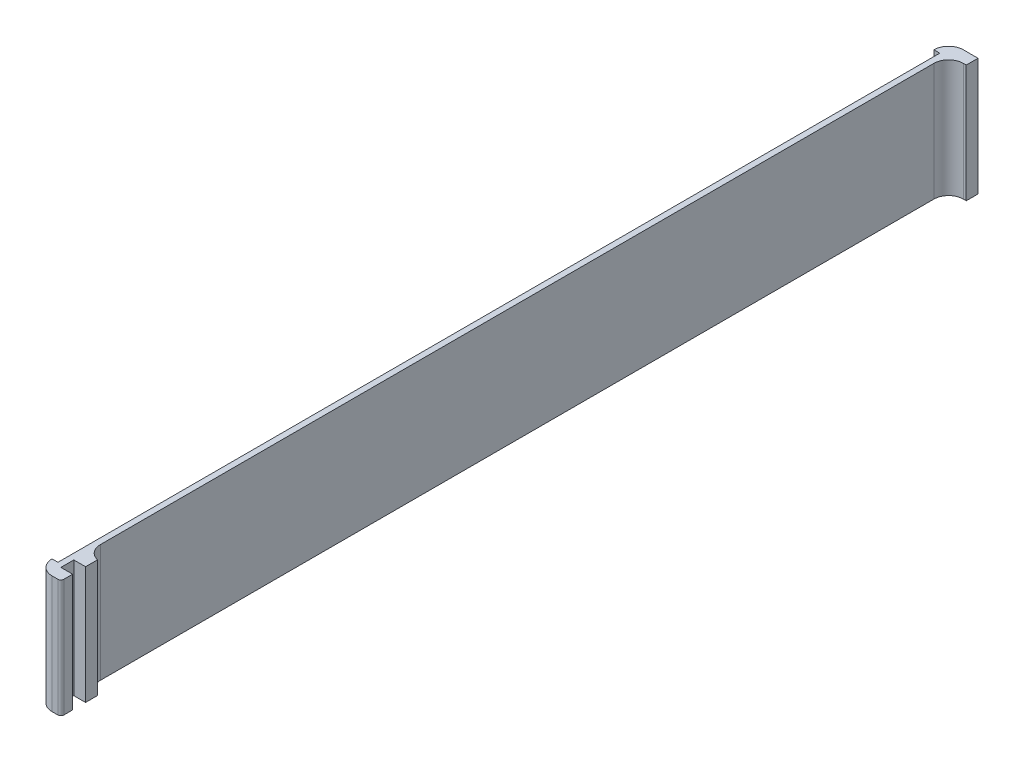
SolidWorks part; units mm, degrees
ref_plane "Front Plane" through (0, 0, 0) normal (0, 0, 1) x (1, 0, 0)
ref_plane "Top Plane" through (0, 0, 0) normal (0, 1, 0) x (1, 0, 0)
ref_plane "Right Plane" through (0, 0, 0) normal (1, 0, 0) x (0, 0, -1)
sketch "Sketch1" plane through (0, 0, 0) normal (0, 1, 0) x (1, 0, 0)
  line L1 (-19.5, 77.5) -> (19.5, 77.5)
  line L2 (-19.5, 77.5) -> (-19.5, -77.5)
  line L3 (-19.5, -77.5) -> (19.5, -77.5)
  line L4 (19.5, 77.5) -> (19.5, -77.5)
  line L5 (-19.5, 77.5) -> (19.5, -77.5) construction
  line L6 (-19.5, -77.5) -> (19.5, 77.5) construction
  point P0 (0, 0)
  dimension "D1" = 39
  dimension "D2" = 155
extrude "Boss-Extrude1" add sketch "Sketch1" along normal blind 2
sketch "Sketch2" plane through (0, 2, 0) normal (0, 1, 0) x (1, 0, 0)
  line L0 (-17.5, -75.5) -> (-17.5, -77.5)
  line L1 (-19.5, 77.5) -> (19.5, 77.5)
  line L2 (-19.5, 77.5) -> (-19.5, -77.5)
  line L3 (-19.5, -77.5) -> (19.5, -77.5)
  line L4 (19.5, 77.5) -> (19.5, -77.5)
  line L5 (-17.5, 75.5) -> (17.5, 75.5)
  line L6 (-17.5, 75.5) -> (-17.5, -75.5)
  line L7 (-17.5, -75.5) -> (17.5, -75.5)
  line L8 (17.5, 75.5) -> (17.5, -75.5)
  line L9 (-17.5, 75.5) -> (17.5, -75.5) construction
  line L10 (-17.5, -75.5) -> (17.5, 75.5) construction
  line L11 (17.5, -75.5) -> (17.5, -77.5)
  point P6 (0, 0)
  line M9 (19.5, -77.5) -> (19.5, 77.5)
  line M10 (19.5, 77.5) -> (-19.5, 77.5)
  line M11 (-19.5, 77.5) -> (-19.5, -77.5)
  line M12 (-19.5, -77.5) -> (19.5, -77.5)
  dimension "D1" = 2
  dimension "D2" = 2
extrude "Boss-Extrude2" add sketch "Sketch2" along normal blind 38 contours L8 L11 L3 L0 L6 L5 M9 M10 M11 M12 region at (-19.0983, 2, 76.5)
sketch "Sketch3" plane through (0, 2, 0) normal (0, 1, 0) x (1, 0, 0)
  line L0 (-17.5, 75.5) -> (-17.5, -77.5) construction
  line L1 (-17.5, -77.5) -> (-15.5, -77.5)
  line L2 (-17.5, -77.5) -> (-17.5, -75.5)
  line L3 (-17.5, -75.5) -> (-15.5, -75.5)
  line L4 (-15.5, -77.5) -> (-15.5, -75.5)
  line L5 (-17.5, -73.3) -> (-15.5, -73.3)
  line L6 (-17.5, -73.3) -> (-17.5, -71.3)
  line L7 (-17.5, -71.3) -> (-15.5, -71.3)
  line L8 (-15.5, -73.3) -> (-15.5, -71.3)
  line L9 (17.5, 75.5) -> (17.5, -77.5) construction
  line L10 (17.5, -77.5) -> (15.5, -77.5)
  line L11 (17.5, -77.5) -> (17.5, -75.5)
  line L12 (17.5, -75.5) -> (15.5, -75.5)
  line L13 (15.5, -77.5) -> (15.5, -75.5)
  line L14 (17.5, -73.3) -> (15.5, -73.3)
  line L15 (17.5, -73.3) -> (17.5, -71.3)
  line L16 (17.5, -71.3) -> (15.5, -71.3)
  line L17 (15.5, -73.3) -> (15.5, -71.3)
  line L18 (15.5, -75.5) -> (15.5, -73.3) construction
  line L19 (-15.5, -73.3) -> (15.5, -73.3) construction
  line L20 (-15.5, -75.5) -> (-15.5, -73.3) construction
  line L21 (-15.5, -75.5) -> (15.5, -75.5) construction
  line L22 (15.5, -71.3) -> (-15.5, -71.3) construction
  dimension "D1" = 2
  dimension "D2" = 2
  dimension "D3" = 2.2
  dimension "D4" = 2
extrude "Boss-Extrude3" add sketch "Sketch3" along normal up to surface (38 mm away) up to face at (0, 40, 0.5)
sketch "Sketch4" plane through (0, 0, -75.5) normal (0, 0, 1) x (1, 0, 0)
  line L0 (-17.5, 40) -> (-15.5, 40)
  line L1 (-17.5, 40) -> (17.5, 40) construction
  line L2 (-15.5, 40) -> (-15.5, 38)
  line L3 (-15.5, 38) -> (-17.5, 38)
  line L5 (-17.5, 38) -> (-17.5, 40)
  line L7 (-17.5, 40) -> (-17.5, 2) construction
  line L8 (-15.5, 33.8) -> (-17.5, 31.8)
  line L9 (-17.5, 31.8) -> (-17.5, 35.8)
  line L10 (-15.5, 33.8) -> (-15.5, 35.8)
  line L11 (-15.5, 35.8) -> (-17.5, 35.8)
  line L12 (0, 0) -> (0, 40) construction
  line L13 (15.5, 35.8) -> (17.5, 35.8)
  line L14 (15.5, 33.8) -> (15.5, 35.8)
  line L15 (17.5, 31.8) -> (17.5, 35.8)
  line L16 (15.5, 33.8) -> (17.5, 31.8)
  line L17 (17.5, 38) -> (17.5, 40)
  line L18 (15.5, 38) -> (17.5, 38)
  line L19 (15.5, 40) -> (15.5, 38)
  line L20 (17.5, 40) -> (15.5, 40)
  dimension "D1" = 2
  dimension "D2" = 2
  dimension "D3" = 45
  dimension "D4" = 2.2
  dimension "D5" = 2
extrude "Boss-Extrude4" add sketch "Sketch4" along normal up to surface (153 mm away) up to face at (0, 20.5, 77.5)
sketch "Sketch5" plane through (0, 2, 0) normal (0, 1, 0) x (1, 0, 0)
  line L1 (-15.5, -77.5) -> (15.5, -77.5)
  line L2 (-15.5, -77.5) -> (-15.5, -75.5)
  line L3 (-15.5, -75.5) -> (15.5, -75.5)
  line L4 (15.5, -77.5) -> (15.5, -75.5)
  line L5 (-15.5, -71.3) -> (15.5, -71.3)
  line L6 (-15.5, -71.3) -> (-15.5, -73.3)
  line L7 (-15.5, -73.3) -> (15.5, -73.3)
  line L8 (15.5, -71.3) -> (15.5, -73.3)
sketch "Sketch6" plane through (0, 0, -75.5) normal (0, 0, 1) x (1, 0, 0)
  line L0 (-17.5, 38) -> (-15.5, 38) construction
  line L1 (-17.5, 38) -> (17.5, 38)
  line L2 (-17.5, 38) -> (-17.5, 35.8)
  line L3 (-17.5, 35.8) -> (17.5, 35.8)
  line L4 (17.5, 38) -> (17.5, 35.8)
  line L5 (-17.5, 38) -> (-17.5, 35.8) construction
  line L6 (-15.5, 35.8) -> (-17.5, 35.8) construction
extrude "Cut-Extrude1" cut sketch "Sketch6" along normal through all
sketch "Sketch7" plane through (0, 2, 0) normal (0, 1, 0) x (1, 0, 0)
  line L1 (-17.5, -75.5) -> (17.5, -75.5)
  line L2 (-17.5, -75.5) -> (-17.5, -73.3)
  line L3 (-17.5, -73.3) -> (17.5, -73.3)
  line L4 (17.5, -75.5) -> (17.5, -73.3)
extrude "Cut-Extrude2" cut sketch "Sketch7" along normal through all
extrude "Boss-Extrude5" add sketch "Sketch5" along normal blind 2
sketch "Sketch8" plane through (0, 0, 0) normal (1, 0, 0) x (0, 0, -1)
  line L0 (75.5, 40) -> (73.5, 40)
  line L1 (-73.3, 40) -> (75.5, 40) construction
  line L2 (73.5, 40) -> (73.5, 38)
  line L3 (-73.3, 38) -> (75.5, 38) construction
  line L4 (73.5, 38) -> (75.5, 38)
  line L5 (75.5, 38) -> (75.5, 40)
  line L6 (75.5, 35.8) -> (73.5, 35.8)
  line L7 (-73.3, 35.8) -> (75.5, 35.8) construction
  line L8 (73.5, 35.8) -> (73.5, 33.8)
  line L9 (-71.3, 33.8) -> (75.5, 33.8) construction
  line L10 (73.5, 33.8) -> (75.5, 31.8)
  line L11 (75.5, 31.8) -> (75.5, 35.8)
  dimension "D1" = 2
extrude "Boss-Extrude6" add sketch "Sketch8" along normal up to surface and the other way up to surface up to face at (17.5, 16.9, -2.1) other way up to face at (-17.5, 16.9, -2.1)
sketch "Sketch10" plane through (-17.5, 0, 0) normal (1, 0, 0) x (0, 0, -1)
  line L1 (-75.5, 35.8) -> (-77.5, 35.8)
  line L2 (-75.5, 35.8) -> (-75.5, 38)
  line L3 (-75.5, 38) -> (-77.5, 38)
  line L4 (-77.5, 35.8) -> (-77.5, 38)
  line L5 (-73.3, 40) -> (-75.5, 40)
  line L6 (-73.3, 40) -> (-73.3, 38)
  line L7 (-73.3, 38) -> (-75.5, 38)
  line L8 (-75.5, 40) -> (-75.5, 38)
  line M1 (-75.5, 40) -> (-75.5, 38)
  line M2 (-75.5, 38) -> (-77.5, 38)
  line M3 (-77.5, 38) -> (-77.5, 35.8)
  line M4 (-77.5, 35.8) -> (-75.5, 35.8)
  line M11 (-73.3, 38) -> (-73.3, 40)
  line M12 (-73.3, 40) -> (-75.5, 40)
extrude "Boss-Extrude8" add sketch "Sketch10" along normal up to surface (2 mm away) contours L2 M4 M2 M3 | L7 M11 M12 M1 region at (-17.5, 39, 74.4) region at (-17.5, 36.9, 76.5) up to face at (-15.5, 39, 76.5)
sketch "Sketch11" plane through (17.5, 0, 0) normal (-1, 0, 0) x (0, 0, 1)
  line L1 (75.5, 35.8) -> (77.5, 35.8)
  line L2 (75.5, 35.8) -> (75.5, 38)
  line L3 (75.5, 38) -> (77.5, 38)
  line L4 (77.5, 35.8) -> (77.5, 38)
  line L5 (73.3, 40) -> (75.5, 40)
  line L6 (73.3, 40) -> (73.3, 38)
  line L7 (73.3, 38) -> (75.5, 38)
  line L8 (75.5, 40) -> (75.5, 38)
  line M2 (75.5, 35.8) -> (77.5, 35.8)
  line M3 (77.5, 35.8) -> (77.5, 38)
  line M4 (77.5, 38) -> (75.5, 38)
  line M5 (75.5, 38) -> (75.5, 40)
  line M6 (75.5, 40) -> (73.3, 40)
  line M7 (73.3, 40) -> (73.3, 38)
extrude "Boss-Extrude9" add sketch "Sketch11" along normal up to surface (2 mm away) contours L2 M2 M3 M4 | L7 M7 M5 M6 region at (17.5, 36.9, 76.5) region at (17.5, 39, 74.4) up to face at (15.5, 39, -0.1)
fillet "Fillet2" radius 2.5 17 edges at (-17.5, 16.9, 71.3) (17.5, 16.9, 71.3) (19.5, 20, 77.5) (-19.5, 20, 77.5) (-19.5, 20, -77.5) (-17.5, 16.9, -75.5) (17.5, 16.9, -75.5) (19.5, 20, -77.5) (-19.5, 40, 0) (0, 40, -77.5) (19.5, 40, 0) (0, 0, -77.5) (0, 0, 77.5) (-19.5, 0, 0) (19.5, 0, 0) (-17.5, 40, 77.5) (17.5, 40, 77.5)
sketch "Sketch13" plane through (0, 0, -77.5) normal (0, 0, -1) x (-1, 0, 0)
  line L0 (15.5, 37.5) -> (15.5, 4) construction
  line L1 (-15.5, 7) -> (15.5, 7)
  line L2 (-15.5, 7) -> (-15.5, 4)
  line L3 (-15.5, 4) -> (15.5, 4)
  line L4 (15.5, 7) -> (15.5, 4)
  dimension "D1" = 3
sketch "Sketch14" plane through (0, 0, -75.5) normal (0, 0, 1) x (1, 0, 0)
  line L1 (-18.25, 9) -> (18.25, 9)
  line L2 (-18.25, 9) -> (-18.25, 1.25)
  line L3 (-18.25, 1.25) -> (18.25, 1.25)
  line L4 (18.25, 9) -> (18.25, 1.25)
  line L5 (15.5, 7) -> (-15.5, 7) construction
  line L7 (17, 0) -> (17, 2.5) construction
  line L8 (19.5, 2.5) -> (17, 2.5) construction
  line L10 (-19.5, 2.5) -> (-17, 2.5) construction
  point P20 (17, 1.25)
  point P23 (18.25, 2.5)
  point P26 (-18.25, 2.5)
  dimension "D1" = 2
extrude "Boss-Extrude10" add sketch "Sketch14" along normal blind 2
extrude "Cut-Extrude4" cut sketch "Sketch13" against normal blind 2
fillet "Fillet3" radius 2 1 edges at (0, 9, -73.5)
fillet "Fillet4" radius 0.5 12 edges at (0, 4, -77.5) (0, 7, -77.5) (15.5, 7, -76.5) (15.5, 4, -76.5) (15.5, 5.5, -77.5) (-15.5, 4, -76.5) (-15.5, 7, -76.5) (-15.5, 5.5, -77.5) (0, 7, -75.5) (-15.5, 5.5, -75.5) (0, 4, -75.5) (15.5, 5.5, -75.5)
sketch "Sketch15" plane through (0, 0, 0) normal (0, -1, 0) x (1, 0, 0)
  line L0 (0, 77.5) -> (0, 0) construction
  line L1 (-17, 77.5) -> (17, 77.5) construction
  line L2 (0, 0) -> (0, -77.5) construction
  line L4 (17, -77.5) -> (-17, -77.5) construction
  circle A0 centre (0, 38.75) radius 5.1
  circle A1 centre (0, -38.75) radius 5.1
  dimension "D1" = 10.2
extrude "Cut-Extrude5" cut sketch "Sketch15" against normal through all
sketch "Sketch16" plane through (0, 2, 0) normal (0, 1, 0) x (1, 0, 0)
  circle A0 centre (0, 38.75) radius 7.1
  circle A1 centre (0, -38.75) radius 7.1
  circle A2 centre (0, 38.75) radius 5.1 construction
  dimension "D1" = 2
extrude "Boss-Extrude11" add sketch "Sketch16" along normal blind 1
fillet "Fillet5" radius 0.5 4 edges at (0, 2, 45.85) (0, 2, -31.65) (0, 3, 45.85) (0, 3, -31.65)
sketch "Sketch12" plane through (0, 0, -75.5) normal (0, 0, 1) x (1, 0, 0)
  line L0 (0, 0) -> (0, 40) construction
  line L1 (15.5, 40) -> (-15.5, 40) construction
  line L2 (0, 20) -> (-10, 20)
  line L3 (0, 20) -> (-9.0097, 15.6612)
  line L4 (0, 20) -> (-6.2349, 12.1817)
  line L5 (0, 20) -> (-2.2252, 10.2507)
  line L6 (0, 20) -> (2.2252, 10.2507)
  line L7 (0, 20) -> (6.2349, 12.1817)
  line L8 (0, 20) -> (9.0097, 15.6612)
  line L9 (0, 20) -> (10, 20)
  line L10 (0, 20) -> (9.0097, 24.3388)
  line L11 (0, 20) -> (6.2349, 27.8183)
  line L12 (0, 20) -> (2.2252, 29.7493)
  line L13 (0, 20) -> (-2.2252, 29.7493)
  line L14 (0, 20) -> (-6.2349, 27.8183)
  line L15 (0, 20) -> (-9.0097, 24.3388)
  circle A0 centre (0, 20) radius 10
  circle A1 centre (0, 20) radius 7.5
  circle A2 centre (0, 20) radius 5
  circle A3 centre (0, 20) radius 2.5
  point P26 (0, 20)
  dimension "D1" = 20
  dimension "D2" = 2.5
  dimension "D3" = 2.5
  dimension "D4" = 2.5
  dimension "D5" = 14
extrude "Cut-Extrude3" cut sketch "Sketch12" against normal through all contours A1 L6 A0 L7 | A1 L4 A0 L5 | A1 L2 A0 L3 | A1 L14 A0 L15 | A1 L0 A0 L13 | L0 A1 L12 A0 | A1 L10 A0 L11 | A1 L8 A0 L9 | A3 L8 A2 L9 | A3 L10 A2 L11 | L0 A3 L12 A2 | A3 L0 A2 L13 | A3 L14 A2 L15 | A3 L2 A2 L3 | A3 L4 A2 L5 | A3 L6 A2 L7 region at (-3.7903, 12.1293, -75.5) region at (3.7903, 12.1293, -75.5) region at (-1.6732, 16.5256, -75.5) region at (1.6732, 16.5256, -75.5) region at (-8.5168, 18.0561, -75.5) region at (8.5168, 18.0561, -75.5) region at (-0.4345, 23.8563, -75.5) region at (0.4345, 23.8563, -75.5) region at (-3.7596, 19.1419, -75.5) region at (3.7596, 19.1419, -75.5) region at (3.015, 22.4044, -75.5) region at (-3.015, 22.4044, -75.5) region at (-6.8299, 25.4467, -75.5) region at (6.8299, 25.4467, -75.5) region at (-0.9843, 28.7358, -75.5) region at (0.9843, 28.7358, -75.5)
fillet "Fillet6" radius 0.4 112 edges at (5.4555, 26.841, -77.5) (7.8183, 26.2349, -77.5) (7.8835, 23.7965, -77.5) (5.8637, 24.6762, -77.5) (3.75, 20, -77.5) (4.8746, 18.8874, -77.5) (3.3786, 18.3729, -77.5) (2.4373, 19.4437, -77.5) (-1.9471, 28.5306, -77.5) (0, 30, -77.5) (1.9471, 28.5306, -77.5) (0, 27.5, -77.5) (-7.8835, 16.2035, -77.5) (-9.7493, 17.7748, -77.5) (-8.75, 20, -77.5) (-7.312, 18.3311, -77.5) (2.3381, 17.0681, -77.5) (2.1694, 15.4952, -77.5) (0.8345, 16.344, -77.5) (1.0847, 17.7476, -77.5) (-0.8345, 16.344, -77.5) (-2.1694, 15.4952, -77.5) (-2.3381, 17.0681, -77.5) (-1.0847, 17.7476, -77.5) (5.4555, 13.159, -77.5) (4.3388, 10.9903, -77.5) (1.9471, 11.4694, -77.5) (3.2541, 13.2427, -77.5) (0, 22.5, -77.5) (-0.8345, 23.656, -77.5) (0, 25, -77.5) (0.8345, 23.656, -77.5) (-3.3786, 21.6271, -77.5) (-3.9092, 23.1174, -77.5) (-2.3381, 22.9319, -77.5) (-1.9546, 21.5587, -77.5) (-3.3786, 18.3729, -77.5) (-4.8746, 18.8874, -77.5) (-3.75, 20, -77.5) (-2.4373, 19.4437, -77.5) (-1.9471, 11.4694, -77.5) (-4.3388, 10.9903, -77.5) (-5.4555, 13.159, -77.5) (-3.2541, 13.2427, -77.5) (-7.8835, 23.7965, -77.5) (-7.8183, 26.2349, -77.5) (-5.4555, 26.841, -77.5) (-5.8637, 24.6762, -77.5) (2.3381, 22.9319, -77.5) (3.9092, 23.1174, -77.5) (3.3786, 21.6271, -77.5) (1.9546, 21.5587, -77.5) (8.75, 20, -77.5) (9.7493, 17.7748, -77.5) (7.8835, 16.2035, -77.5) (7.312, 18.3311, -77.5) (7.8835, 23.7965, -75.5) (7.8183, 26.2349, -75.5) (5.4555, 26.841, -75.5) (5.8637, 24.6762, -75.5) (3.3786, 18.3729, -75.5) (4.8746, 18.8874, -75.5) (3.75, 20, -75.5) (2.4373, 19.4437, -75.5) (1.9471, 28.5306, -75.5) (0, 30, -75.5) (-1.9471, 28.5306, -75.5) (0, 27.5, -75.5) (-8.75, 20, -75.5) (-9.7493, 17.7748, -75.5) (-7.8835, 16.2035, -75.5) (-7.312, 18.3311, -75.5) (0.8345, 16.344, -75.5) (2.1694, 15.4952, -75.5) (2.3381, 17.0681, -75.5) (1.0847, 17.7476, -75.5) (-2.3381, 17.0681, -75.5) (-2.1694, 15.4952, -75.5) (-0.8345, 16.344, -75.5) (-1.0847, 17.7476, -75.5) (1.9471, 11.4694, -75.5) (4.3388, 10.9903, -75.5) (5.4555, 13.159, -75.5) (3.2541, 13.2427, -75.5) (0, 22.5, -75.5) (0.8345, 23.656, -75.5) (0, 25, -75.5) (-0.8345, 23.656, -75.5) (-2.3381, 22.9319, -75.5) (-3.9092, 23.1174, -75.5) (-3.3786, 21.6271, -75.5) (-1.9546, 21.5587, -75.5) (-3.75, 20, -75.5) (-4.8746, 18.8874, -75.5) (-3.3786, 18.3729, -75.5) (-2.4373, 19.4437, -75.5) (-5.4555, 13.159, -75.5) (-4.3388, 10.9903, -75.5) (-1.9471, 11.4694, -75.5) (-3.2541, 13.2427, -75.5) (-5.4555, 26.841, -75.5) (-7.8183, 26.2349, -75.5) (-7.8835, 23.7965, -75.5) (-5.8637, 24.6762, -75.5) (3.3786, 21.6271, -75.5) (3.9092, 23.1174, -75.5) (2.3381, 22.9319, -75.5) (7.8835, 16.2035, -75.5) (9.7493, 17.7748, -75.5) (8.75, 20, -75.5) (7.312, 18.3311, -75.5) (1.9546, 21.5587, -75.5)
fillet "Fillet7" radius 0.5 8 edges at (15.5, 40, 0.75) (15.5, 39.2678, 76.7678) (-15.5, 40, 0.75) (-15.5, 39.2678, 76.7678) (0, 40, -73.5) (15.5, 20.75, 77.5) (-15.5, 20.75, 77.5) (0, 4, 77.5)
sketch "Sketch17" plane through (0, 0, 0) normal (0, -1, 0) x (1, 0, 0)
  line L0 (-17, -77.5) -> (-17, 70.3)
  line L1 (-17, -77.5) -> (17, -77.5)
  line L2 (17, -77.5) -> (17, 70.3)
  line L3 (17, -75) -> (17, 75) construction
  line L5 (17, 70.3) -> (15, 71.3)
  line L6 (15, 71.3) -> (15, 77.5)
  line L7 (15, 77.5) -> (-15, 77.5)
  line L8 (-15, 77.5) -> (-15, 71.3)
  line L9 (-15, 71.3) -> (-17, 70.3)
  line L10 (-17, 75) -> (-17, -75) construction
  line L12 (-15, 71.3) -> (15, 71.3) construction
  line L13 (17, 70.3) -> (-17, 70.3) construction
  line L14 (0, 71.3) -> (0, 77.5) construction
  line L15 (-17, 77.5) -> (17, 77.5) construction
  arc A0 (-19.5, -75) -> (-17, -77.5) centre (-17, -75) ccw construction
  dimension "D1" = 1
  dimension "D2" = 30
  dimension "D3" = 6.2
extrude "Cut-Extrude6" cut sketch "Sketch17" against normal blind 6
sketch "Sketch18" plane through (0, 0, 0) normal (0, 0, 1) x (1, 0, 0)
  line L0 (15, 9) -> (-15, 9) construction
  line L1 (-14.5, 9) -> (14.5, 9)
  line L2 (-14.5, 9) -> (-14.5, 6)
  line L3 (-14.5, 6) -> (14.5, 6)
  line L4 (14.5, 9) -> (14.5, 6)
  line L5 (-17, 6) -> (17, 6) construction
  line L6 (0, 6) -> (0, 0) construction
  dimension "D1" = 29
extrude "Cut-Extrude8" cut sketch "Sketch18" against normal through all
sketch "Sketch20" plane through (0, 0, 0) normal (0, 0, 1) x (1, 0, 0)
  line L0 (-16, 40) -> (16, 40) construction
  line L1 (-19.5, 40) -> (-14.5, 40)
  line L2 (-19.5, 40) -> (-19.5, 0)
  line L3 (-19.5, 0) -> (-14.5, 0)
  line L4 (-14.5, 40) -> (-14.5, 0)
  line L5 (-14.5, 6) -> (14.5, 6)
  line L6 (-14.5, 6) -> (-14.5, 40)
  line L7 (-14.5, 40) -> (14.5, 40)
  line L8 (14.5, 6) -> (14.5, 40)
  line L9 (14.5, 40) -> (19.5, 40)
  line L10 (14.5, 40) -> (14.5, 0)
  line L11 (14.5, 0) -> (19.5, 0)
  line L12 (19.5, 40) -> (19.5, 0)
  line L13 (-15, 0) -> (-17, 0) construction
  line L14 (-19.5, 2.5) -> (-19.5, 37.5) construction
  line L15 (17, 0) -> (15, 0) construction
  line L16 (19.5, 37.5) -> (19.5, 2.5) construction
extrude "Cut-Extrude11" cut sketch "Sketch20" against normal through all both and the other way through all contours L5 L8 L7 L4 | L12 L9 L8 L10 L11 region at (0, 23, 0) region at (17, 20, 0)
sketch "Sketch21" plane through (0, 0, 0) normal (1, 0, 0) x (0, 0, -1)
  line L0 (77.5, 37.5) -> (77.5, 7.5) construction
  line L1 (-77.5, 40) -> (77.5, 40)
  line L2 (-77.5, 40) -> (-77.5, 30)
  line L3 (-77.5, 30) -> (77.5, 30)
  line L4 (77.5, 40) -> (77.5, 30)
  line L5 (77.5, 30) -> (-77.5, 30)
  line L6 (77.5, 30) -> (77.5, 10)
  line L7 (77.5, 10) -> (-77.5, 10)
  line L8 (-77.5, 30) -> (-77.5, 10)
  line L9 (-77.5, 10) -> (77.5, 10)
  line L10 (-77.5, 10) -> (-77.5, 0)
  line L11 (-77.5, 0) -> (77.5, 0)
  line L12 (77.5, 10) -> (77.5, 0)
  line L13 (-70.3, 0) -> (75, 0) construction
  line L14 (-77.5, 3.5) -> (-77.5, 2.5) construction
  line L15 (-75, 40) -> (74, 40) construction
  line L16 (77.5, 30) -> (77.5, 10)
  line L17 (-77.5, 10) -> (-77.5, 30)
  dimension "D1" = 20
  dimension "D2" = 10
extrude "Cut-Extrude12" cut sketch "Sketch21" against normal through all contours L4 L1 L2 L3 | L12 L7 L10 L11 region at (0, 35, 0) region at (0, 5, 0)
sketch "Sketch22" plane through (-19.5, 0, 0) normal (-1, 0, 0) x (0, 0, 1)
  line L1 (-75, 30) -> (75, 30)
  line L2 (-75, 30) -> (-75, 10)
  line L3 (-75, 10) -> (75, 10)
  line L4 (75, 30) -> (75, 10)
extrude "Cut-Extrude13" cut sketch "Sketch22" against normal blind 1
